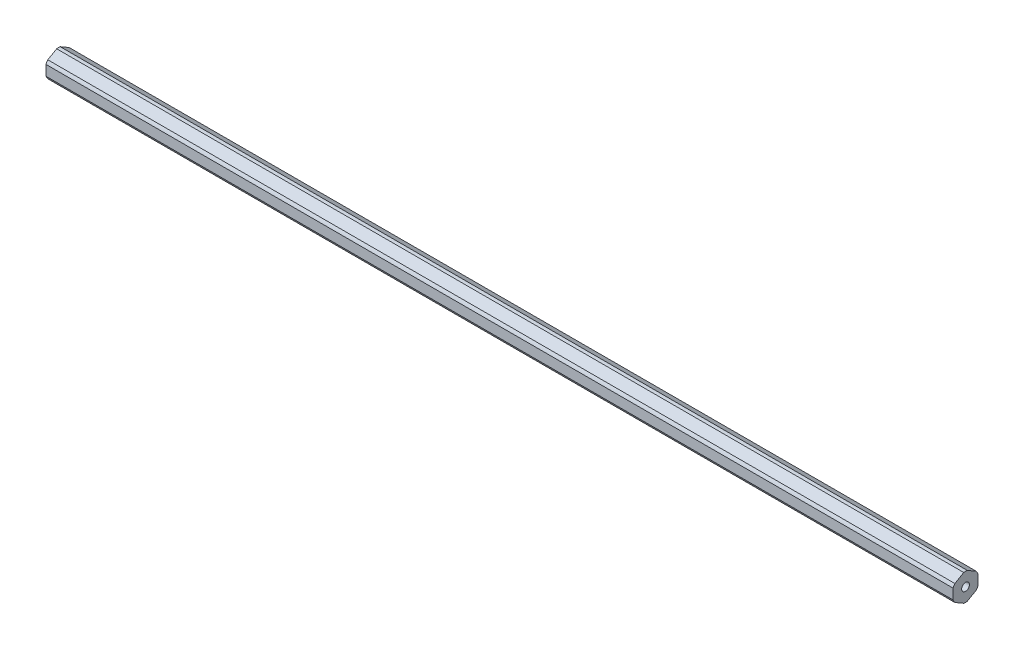
SolidWorks part; units mm, degrees
material "6061 Alloy"
ref_plane "Front Plane" through (0, 0, 0) normal (0, 0, 1) x (1, 0, 0)
ref_plane "Top Plane" through (0, 0, 0) normal (0, 1, 0) x (1, 0, 0)
ref_plane "Right Plane" through (0, 0, 0) normal (1, 0, 0) x (0, 0, -1)
ref_plane "Plane1" through (914.4, 0, 0) normal (1, 0, 0) x (0, 0, -1)
sketch "Sketch1" plane through (914.4, 0, 0) normal (1, 0, 0) x (0, 0, -1)
  line L0 (-5.4343, -4.1949) -> (-0.9157, -6.8037)
  line L1 (0.9157, -6.8037) -> (5.4343, -4.1949)
  line L2 (6.35, -2.6088) -> (6.35, 2.6088)
  line L3 (5.4343, 4.1949) -> (0.9157, 6.8037)
  line L4 (-0.9157, 6.8037) -> (-5.4343, 4.1949)
  line L5 (-6.35, 2.6088) -> (-6.35, -2.6088)
  circle A0 centre (0, 0) radius 1.9939
  arc A1 (-6.35, -2.6088) -> (-5.4343, -4.1949) centre (0, 0) ccw
  arc A2 (-0.9157, -6.8037) -> (0.9157, -6.8037) centre (0, 0) ccw
  arc A3 (5.4343, -4.1949) -> (6.35, -2.6088) centre (0, 0) ccw
  arc A4 (6.35, 2.6088) -> (5.4343, 4.1949) centre (0, 0) ccw
  arc A5 (0.9157, 6.8037) -> (-0.9157, 6.8037) centre (0, 0) ccw
  arc A6 (-5.4343, 4.1949) -> (-6.35, 2.6088) centre (0, 0) ccw
extrude "Boss-Extrude1" add sketch "Sketch1" against normal blind 462.534
equation "\"Hex Length\"= 18.21"
equation "\"D1@Boss-Extrude1\"=\"Hex Length\""
